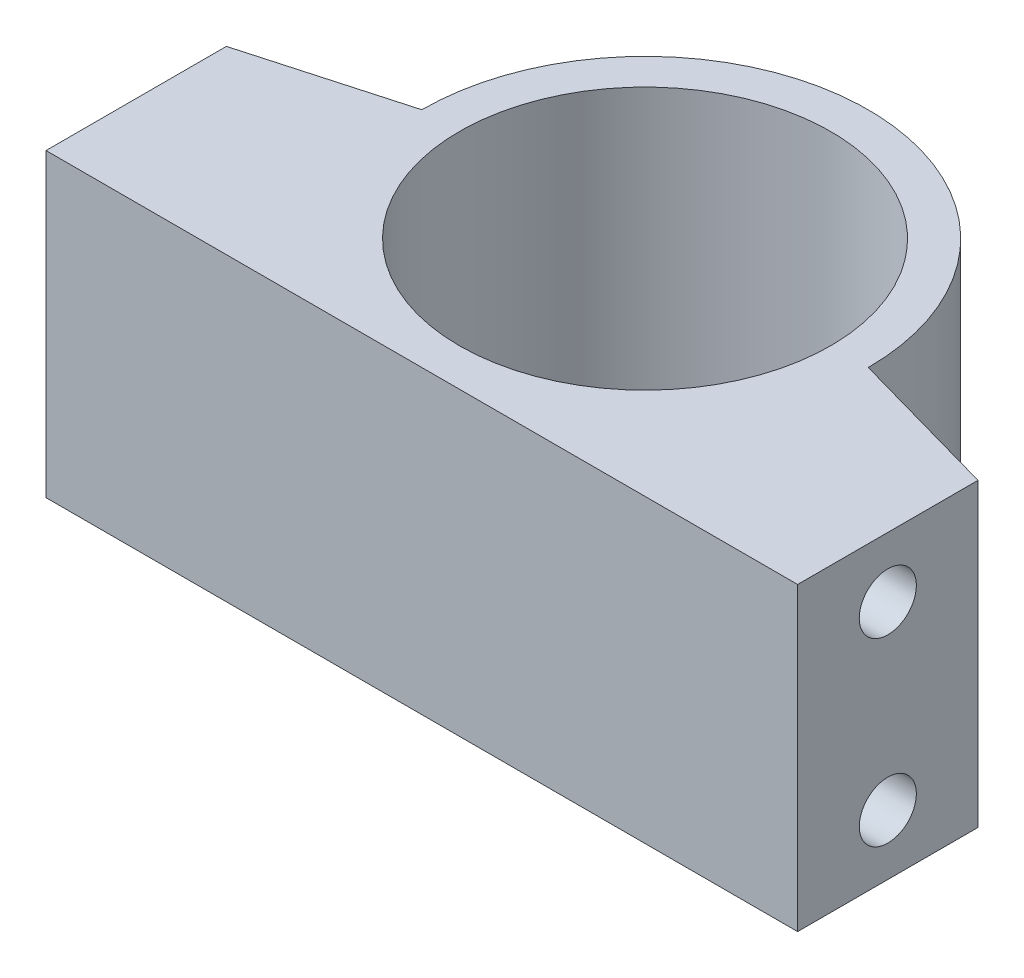
SolidWorks part; units mm, degrees
ref_plane "Front Plane" through (0, 0, 0) normal (0, 0, 1) x (1, 0, 0)
ref_plane "Top Plane" through (0, 0, 0) normal (0, 1, 0) x (1, 0, 0)
ref_plane "Right Plane" through (0, 0, 0) normal (1, 0, 0) x (0, 0, -1)
sketch "Sketch1" plane through (0, 0, 0) normal (0, 1, 0) x (1, 0, 0)
  line L0 (-14.85, 0) -> (-25, -2.85)
  line L1 (-25, -2.85) -> (-25, -14.85)
  line L2 (-25, -14.85) -> (0, -14.85)
  line L3 (-45.7349, 0) -> (45.7349, 0) construction
  line L4 (0, -8.35) -> (0, 8.35) construction
  circle A0 centre (0, 0) radius 12.35
  arc A1 (0, -14.85) -> (-14.85, 0) centre (0, 0) ccw
  circle A5 centre (0, 8.35) radius 1.35
  circle A6 centre (0, -8.35) radius 1.35
  circle A7 centre (0, 0) radius 4.5
  point P0 (0, -14.85)
  point P7 (0, 0)
  point P11 (0, 0)
  point P12 (-14.2894, -3.8541)
  point P15 (-14.8, 0)
  point P17 (0, 0)
  dimension "D1" = 24.7
  dimension "D2" = 2.5
  dimension "D6" = 2.7
  dimension "D8" = 9
  dimension "D4" = 12
  dimension "D5" = 25
  dimension "D7" = 16.7
extrude "Boss-Extrude1" add sketch "Sketch1" along normal blind 20 contours L2 A1 L0 L1 A0 region at (10.1491, 0, -10.1491)
extrude "Boss-Extrude2" add sketch "Sketch1<5>" along normal blind 1.7 contours A0 A7 A6 A5 region at (-12.0007, 0, 0)
sketch "Sketch1<5>" plane through (0, 0, 0) normal (0, 1, 0) x (1, 0, 0) same geometry as "Sketch1"
mirror "Mirror1" about plane through (0, 0, 0) normal (1, 0, 0) of "Boss-Extrude1"
sketch "Sketch2" plane through (0, 0, 0) normal (1, 0, 0) x (0, 0, -1)
  line L0 (-8.85, 4) -> (-8.85, 16) construction
  line L1 (14.85, 10) -> (17.3611, 10) construction
  line L2 (14.85, 0) -> (14.85, 20) construction
  line L3 (-14.85, 10) -> (-2.85, 10) construction
  line L4 (-14.85, 20) -> (-14.85, 0) construction
  line L5 (-2.85, 20) -> (-2.85, 0) construction
  circle A0 centre (-8.85, 4) radius 1.9
  circle A1 centre (-8.85, 16) radius 1.9
  point P7 (-8.85, 10)
  point P16 (-8.85, 10)
  dimension "D1" = 3.8
  dimension "D2" = 4
extrude "Cut-Extrude1" cut sketch "Sketch2" against normal blind 30 and the other way blind 32
sketch "Sketch4" plane through (0, 0, 0) normal (0, 1, 0) x (1, 0, 0)
  line L1 (-15.0193, 4.9792) -> (-15.0193, -4.9792)
  line L2 (-15.0193, -4.9792) -> (-21.1412, -3.3467)
  line L3 (-21.1412, -3.3467) -> (-21.1412, 3.3467)
  line L4 (-21.1412, 3.3467) -> (-15.0193, 4.9792)
  point P2 (-15.0193, 0)
  point P4 (-21.1412, 0)
extrude "Cut-Extrude3" [suppressed] cut sketch "Sketch4" along normal up to surface (20 mm away)
mirror "Mirror2" [suppressed] about plane through (0, 0, 0) normal (1, 0, 0)
